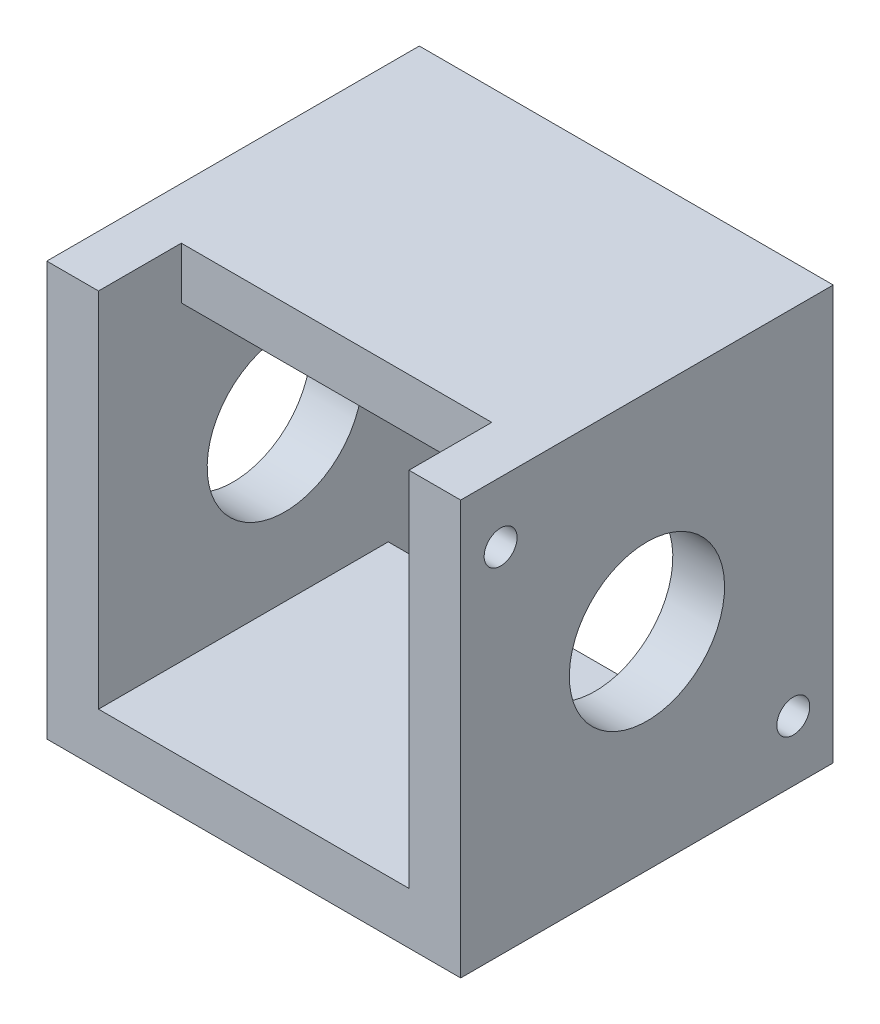
SolidWorks part; units mm, degrees
ref_plane "Front Plane" through (0, 0, 0) normal (0, 0, 1) x (1, 0, 0)
ref_plane "Top Plane" through (0, 0, 0) normal (0, 1, 0) x (1, 0, 0)
ref_plane "Right Plane" through (0, 0, 0) normal (1, 0, 0) x (0, 0, -1)
sketch "Sketch1" plane through (0, 0, 0) normal (0, 0, 1) x (1, 0, 0)
  line L1 (-25.4, 25.4) -> (25.4, 25.4)
  line L2 (-25.4, 25.4) -> (-25.4, -25.4)
  line L3 (-25.4, -25.4) -> (25.4, -25.4)
  line L4 (25.4, 25.4) -> (25.4, -25.4)
  line L5 (-25.4, 25.4) -> (25.4, -25.4) construction
  line L6 (-25.4, -25.4) -> (25.4, 25.4) construction
  point P0 (0, 0)
  dimension "D1" = 50.8
  dimension "D2" = 50.8
extrude "Extrude-Thin1" add sketch "Sketch1" along normal blind 45.72 thin thin type one direction reverse wall 6.35
sketch "Sketch2" plane through (25.4, 0, 0) normal (1, 0, 0) x (0, 0, -1)
  line L1 (-4.8995, -25.4) -> (-4.8995, -17.9605) construction
  line L3 (-4.8995, -17.9605) -> (0, -17.9605) construction
  line L5 (-45.72, 17.9605) -> (-40.8205, 17.9605) construction
  line L7 (-40.8205, 17.9605) -> (-40.8205, 25.4) construction
  line L8 (-45.72, 25.4) -> (0, 25.4) construction
  line L9 (0, -25.4) -> (0, 25.4) construction
  line L10 (-45.72, -25.4) -> (0, -25.4) construction
  line L11 (-45.72, -25.4) -> (-45.72, 25.4) construction
  circle A2 centre (-40.8205, 17.9605) radius 2.0193
  circle A3 centre (-4.8995, -17.9605) radius 2.0193
  dimension "D1" = 4.0386
  dimension "D2" = 7.4395
  dimension "D3" = 4.8995
extrude "Cut-Extrude2" cut sketch "Sketch2" along direction (-1, 0, 0) on the side against the normal up to surface (6.35 mm away) and the other way through all up to face at (19.05, 0, 22.86)
sketch "Sketch4" plane through (25.4, 0, 0) normal (1, 0, 0) x (0, 0, -1)
  line L0 (-45.72, -25.4) -> (0, -25.4) construction
  circle A0 centre (-22.86, 0) radius 9.525
  point P7 (-22.86, -25.4)
  dimension "D1" = 19.05
extrude "Cut-Extrude3" cut sketch "Sketch4" against normal through all both and the other way through all
sketch "Sketch5" plane through (0, -25.4, 0) normal (0, -1, 0) x (1, 0, 0)
  line L0 (-25.4, 0) -> (25.4, 0) construction
  line L1 (19.05, 0) -> (-19.05, 0)
  line L2 (19.05, 0) -> (19.05, 10.16)
  line L3 (19.05, 10.16) -> (-19.05, 10.16)
  line L4 (-19.05, 0) -> (-19.05, 10.16)
  line L5 (25.4, 45.72) -> (25.4, 0) construction
  line L6 (-25.4, 45.72) -> (-25.4, 0) construction
  line L7 (25.4, 22.86) -> (-25.4, 22.86) construction
  line L8 (19.05, 45.72) -> (-19.05, 45.72)
  line L9 (19.05, 45.72) -> (19.05, 35.56)
  line L10 (-19.05, 45.72) -> (-19.05, 35.56)
  line L11 (19.05, 35.56) -> (-19.05, 35.56)
  line M5 (-25.4, 0) -> (25.4, 0)
  line M7 (25.4, 45.72) -> (-25.4, 45.72)
  dimension "D1" = 10.16
  dimension "D2" = 6.35
  dimension "D3" = 6.35
extrude "Cut-Extrude4" cut sketch "Sketch5" against normal up to next and the other way through all contours L4 L2 L3 M5 region at (0, -25.4, 5.08)
extrude "Cut-Extrude5" cut sketch "Sketch5<3>" against normal up to surface (50.8 mm away) from offset 25.4 contours L11 L9 L10 M7 region at (0, -25.4, 40.64) up to face at (0, 25.4, 22.86) offset against normal yes
sketch "Sketch5<3>" plane through (0, -25.4, 0) normal (0, -1, 0) x (1, 0, 0) same geometry as "Sketch5"
